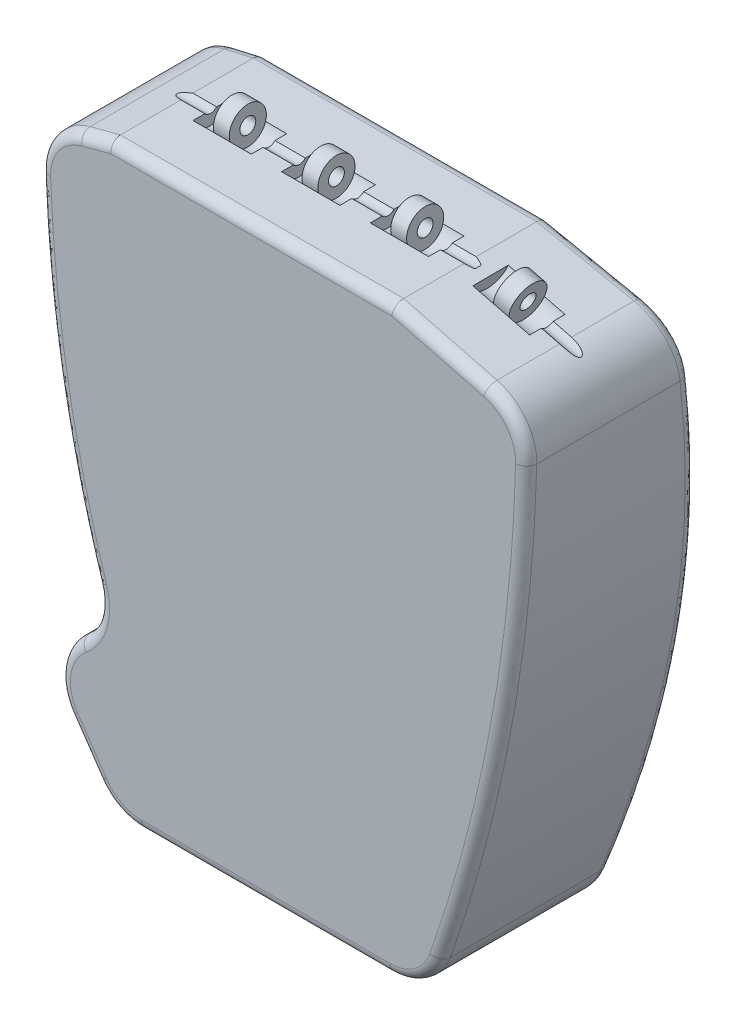
SolidWorks part; units mm, degrees
ref_plane "Front Plane" through (0, 0, 0) normal (0, 0, 1) x (1, 0, 0)
ref_plane "Top Plane" through (0, 0, 0) normal (0, 1, 0) x (1, 0, 0)
ref_plane "Right Plane" through (0, 0, 0) normal (1, 0, 0) x (0, 0, -1)
sketch "Sketch1" plane through (0, 0, 0) normal (0, 0, 1) x (1, 0, 0)
  line L1 (0, 0) -> (92, 0)
  line L2 (0, 0) -> (0, 110)
  line L3 (0, 110) -> (92, 110)
  line L4 (92, 0) -> (92, 110)
  dimension "D1" = 110
  dimension "D2" = 92
extrude "Boss-Extrude1" add sketch "Sketch1" along normal mid plane 40
sketch "Sketch2" plane through (0, 0, 20) normal (0, 0, 1) x (1, 0, 0)
  line L0 (0, 106.5) -> (13.3096, 110)
  line L1 (0, 110) -> (0, 0) construction
  line L2 (92, 110) -> (0, 110) construction
  line L3 (13.3096, 110) -> (30.517, 110)
  line L4 (30.517, 110) -> (66.778, 110)
  line L5 (66.778, 110) -> (92, 103.5)
  line L6 (92, 0) -> (92, 110) construction
  line L7 (0, 0) -> (92, 0) construction
  line L8 (14, 0) -> (0, 20.5)
  line L9 (0, 20.5) -> (6.9084, 25.2179)
  arc A0 (6.9084, 25.2179) -> (10.8003, 36.5009) centre (1.2688, 33.476) ccw
  spline S0 degree 2 poles (92, 103.5) (92, 50.0313) (73.1625, 0) knots 0 0 0 1 1 1
  spline S1 degree 3 poles (0, 106.5) (0, 82.6021) (3.5978, 59.1959) (10.8003, 36.5009) knots 0 0 0 0 0.906288 0.906288 0.906288 0.906288
  dimension "D5" = 10
  dimension "D1" = 14
  dimension "D2" = 20.5
  dimension "D3" = 3.5
  dimension "D4" = 6.5
extrude "Cut-Extrude1" cut sketch "Sketch2" against normal through all both and the other way through all
fillet "Fillet1" radius 10 5 edges at (92, 103.5, 0) (73.1625, 0, 0) (0, 20.5, 0) (14, 0, 0) (0, 106.5, 0)
sketch "Sketch3" plane through (0, 0, 0) normal (1, 0, 0) x (0, 0, -1)
  line L0 (7.7727, 115.4433) -> (22.5, 115.4433)
  line L1 (22.5, 115.4433) -> (22.5, -6.8751)
  line L2 (22.5, -6.8751) -> (10.4318, -6.8751)
  spline S0 degree 2 poles (7.7727, 115.4433) (19.5564, 54.5186) (10.4318, -6.8751) knots 0 0 0 1 1 1
  point P5 (-28.6765, 38.1167)
extrude "Cut-Extrude2" cut sketch "Sketch3" along normal through all both and the other way through all
fillet "Fillet2" radius 2 26 edges at (75.5857, 107.7301, 20) (89.8827, 101.7969, 20) (10.4481, 109.2475, 20) (2.1081, 104.7948, 20) (10.8476, 30.6044, 20) (3.9653, 19.3849, 20) (8.312, 8.3288, 20) (14.6109, 1.157, 20) (42.7178, 0, 20) (71.9427, 1.8448, 20) (2.1315, 104.8261, -9.6669) (1.4184, 80.7177, -12.7874) (10.601, 29.883, -14.0232) (4.0909, 20.0738, -13.4316) (13.3524, 1.9463, -11.6353) (42.7178, 0, -11.3883) (72.3656, 2.162, -11.662) (83.2661, 32.2784, -14.127) (89.8299, 101.8663, -10.1382) (40.0438, 110, 20) (40.0438, 110, -8.7837)
sketch "Sketch4" plane through (30.7416, 119.287, 0) normal (0.2496, 0.9684, 0) x (0.9684, -0.2496, 0)
  arc A0 (55.4048, 7.8519) -> (37.2138, 7.0934) centre (282.5293, -5658.0375) ccw construction
  point P0 (46.309, 7.48)
  point P1 (46.309, 32.9917)
sketch "Sketch12" plane through (0, 0, 20) normal (0, 0, 1) x (1, 0, 0)
  line L0 (75.2094, 105.7618) -> (48.4688, 2)
  line L1 (83.8943, 103.5236) -> (66.5244, 108) construction
  line L2 (19.2802, 2) -> (66.1555, 2) construction
ref_plane "Plane4" through (44.8763, -11.5652, -0.2143) normal (0.9683, -0.2496, -0.0046) x (-0.0045, 0.0012, -1)
sketch "Sketch16" plane through (44.8763, -11.5652, -0.2143) normal (0.9683, -0.2496, -0.0046) x (-0.0045, 0.0012, -1)
  line L0 (-5.3302, 123.1846) -> (-5.3302, 127.1846) construction
  line L2 (7.5956, 123.1846) -> (-18.256, 123.1846)
  line L3 (-18.3011, 115.4226) -> (8.7391, 115.4226)
  line L4 (7.5956, 123.1846) -> (-18.256, 123.1846)
  line L5 (-18.3011, 115.4226) -> (8.7391, 115.4226)
  circle A0 centre (-5.3302, 124.1846) radius 3.5
  spline S2 degree 3 poles (-18.256, 123.1846) (-18.2785, 123.1846) (-18.2961, 120.1579) (-18.3011, 115.4226) knots 0 0 0 0 1 1 1 1 weights 1 0.854829 0.854829 1
  spline S3 degree 3 poles (-4.1595, -2884.3814) (26.9994, -331.8571) (16.6333, 51.7638) (8.4312, 118.0289) (8.3088, 118.9842) (8.2494, 119.4312) (8.1348, 120.2618) (8.0795, 120.6462) (7.9737, 121.3508) (7.9243, 121.6628) (7.8336, 122.2033) (7.7921, 122.4329) (7.7178, 122.8075) (7.6857, 122.9484) (5.1153, 132.0299) (51.2682, -279.2704) (467.6836, -2841.148) knots -16.443699 -16.443699 -16.443699 -16.443699 0.125 0.25 0.25 0.375 0.375 0.5 0.5 0.625 0.625 0.75 0.75 0.875 0.875 12.817906 12.817906 12.817906 12.817906 only from (8.7391, 115.4226) to (7.5956, 123.1846)
  spline S4 degree 3 poles (-18.256, 123.1846) (-18.2785, 123.1846) (-18.2961, 120.1579) (-18.3011, 115.4226) knots 0 0 0 0 1 1 1 1 weights 1 0.854829 0.854829 1
  spline S5 degree 3 poles (8.7391, 115.4226) (8.6773, 115.973) (8.554, 117.0365) (8.4312, 118.0289) (8.3088, 118.9842) (8.2494, 119.4312) (8.1348, 120.2618) (8.0795, 120.6462) (7.9737, 121.3508) (7.9243, 121.6628) (7.8336, 122.2033) (7.7921, 122.4329) (7.7178, 122.8075) (7.6857, 122.9484) (7.6324, 123.1365) (7.6112, 123.1846) (7.5956, 123.1846) knots 0 0 0 0 0.125 0.25 0.25 0.375 0.375 0.5 0.5 0.625 0.625 0.75 0.75 0.875 0.875 1 1 1 1
  dimension "D2" = 1
  dimension "D3" = 7
  dimension "D1" = 0
extrude "Boss-Extrude3" add sketch "Sketch16" along normal mid plane 3 contours A0
sketch "Sketch17" plane through (46.3289, -11.9395, -0.2213) normal (0.9683, -0.2496, -0.0046) x (-0.0045, 0.0012, -1)
  circle A0 centre (-5.3302, 124.1846) radius 3.5
extrude "Cut-Extrude4" cut sketch "Sketch17" along normal blind 4
mirror "Mirror2" about plane through (44.8763, -11.5652, -0.2143) normal (0.9683, -0.2496, -0.0046) of "Cut-Extrude4"
sketch "Sketch18" plane through (46.3289, -11.9395, -0.2213) normal (0.9683, -0.2496, -0.0046) x (-0.0045, 0.0012, -1)
  circle A0 centre (-5.3302, 124.1846) radius 1.5
extrude "Cut-Extrude5" cut sketch "Sketch18" against normal blind 4 and the other way through all contours A0
sketch "Sketch19" plane through (0, 110, 0) normal (0, 1, 0) x (1, 0, 0)
  line L0 (66.7779, 7.1044) -> (13.3097, 7.1044) construction
  point P0 (56.7779, 7.1044)
  point P1 (40.0438, 7.1044)
  point P4 (23.3097, 7.1044)
  point P5 (48.4088, 7.1044)
  dimension "D1" = 10
  dimension "D2" = 10
  dimension "D3" = 8.365
ref_plane "Plane6" through (56.7779, 0, 0) normal (1, 0, 0) x (0, 0, -1)
sketch "Sketch20" plane through (56.7779, 0, 0) normal (1, 0, 0) x (0, 0, -1)
  line L0 (-18, 110) -> (7.0934, 110) construction
  line L1 (-18, 110) -> (7.0934, 110)
  line L2 (-5.4533, 110) -> (-5.4533, 112) construction
  circle A0 centre (-5.4533, 111) radius 3.5
  dimension "D1" = 1
extrude "Boss-Extrude4" add sketch "Sketch20" along normal mid plane 3 contours A0
sketch "Sketch21" plane through (58.2779, 0, 0) normal (1, 0, 0) x (0, 0, -1)
  line L0 (-18, 110) -> (7.0934, 110) construction
  circle A0 centre (-5.4533, 111) radius 3.5
extrude "Cut-Extrude6" cut sketch "Sketch21" along normal blind 4
mirror "Mirror3" about plane through (56.7779, 0, 0) normal (1, 0, 0) of "Cut-Extrude6"
sketch "Sketch22" plane through (58.2779, 0, 0) normal (1, 0, 0) x (0, 0, -1)
  circle A0 centre (-5.4533, 111) radius 1.5
  dimension "D1" = 3
ref_plane "Plane7" through (40.0438, 0, 0) normal (1, 0, 0) x (0, 0, -1)
mirror "Mirror4" about plane through (40.0438, 0, 0) normal (1, 0, 0) of "Mirror3", "Boss-Extrude4", "Cut-Extrude6"
ref_plane "Plane8" through (48.4088, 0, 0) normal (1, 0, 0) x (0, 0, -1)
mirror "Mirror5" about plane through (48.4088, 0, 0) normal (1, 0, 0) of "Boss-Extrude4", "Cut-Extrude6", "Mirror3"
sketch "Sketch23" plane through (41.5397, 0, 0) normal (1, 0, 0) x (0, 0, -1)
  circle A0 centre (-5.4533, 111) radius 1.5
extrude "Cut-Extrude8" cut sketch "Sketch23" against normal through all
extrude "Cut-Extrude9" cut sketch "Sketch22" against normal through all and the other way blind 10 contours A0
ref_plane "Plane10" through (10.569, 30.7052, 0.0084) normal (0.3255, 0.9456, 0.0003) x (0.9456, -0.3255, -0.0001)
sketch "Sketch25" plane through (10.569, 30.7052, 0.0084) normal (0.3255, 0.9456, 0.0003) x (0.9456, -0.3255, -0.0001)
  line L0 (-8.5609, -5.4232) -> (-3.1429, -5.4232) construction
  circle A0 centre (-0.6973, -5.4232) radius 3.5
  point P12 (-4.3519, -18.5674)
  dimension "D1" = 1
extrude "Boss-Extrude6" add sketch "Sketch25" along normal mid plane 3
sketch "Sketch26" plane through (10.0808, 29.2869, 0.008) normal (-0.3255, -0.9456, -0.0003) x (0.9456, -0.3255, -0.0001)
  circle A1 centre (-1.1973, 5.4228) radius 3.4996
extrude "Cut-Extrude11" cut sketch "Sketch26" along normal blind 4
mirror "Mirror6" about plane through (10.569, 30.7052, 0.0084) normal (0.3255, 0.9456, 0.0003) of "Cut-Extrude11"
sketch "Sketch27" plane through (10.0808, 29.2869, 0.008) normal (-0.3255, -0.9456, -0.0003) x (0.9456, -0.3255, -0.0001)
  circle A0 centre (-0.6973, 5.4232) radius 1.5
extrude "Cut-Extrude12" cut sketch "Sketch27" against normal blind 7 and the other way blind 10
sketch "Sketch28" plane through (0, 0, 0) normal (0, -1, 0) x (1, 0, 0)
  circle A0 centre (42.7178, 3.2165) radius 10.5
extrude "Cut-Extrude13" cut sketch "Sketch28" against normal blind 2.5
